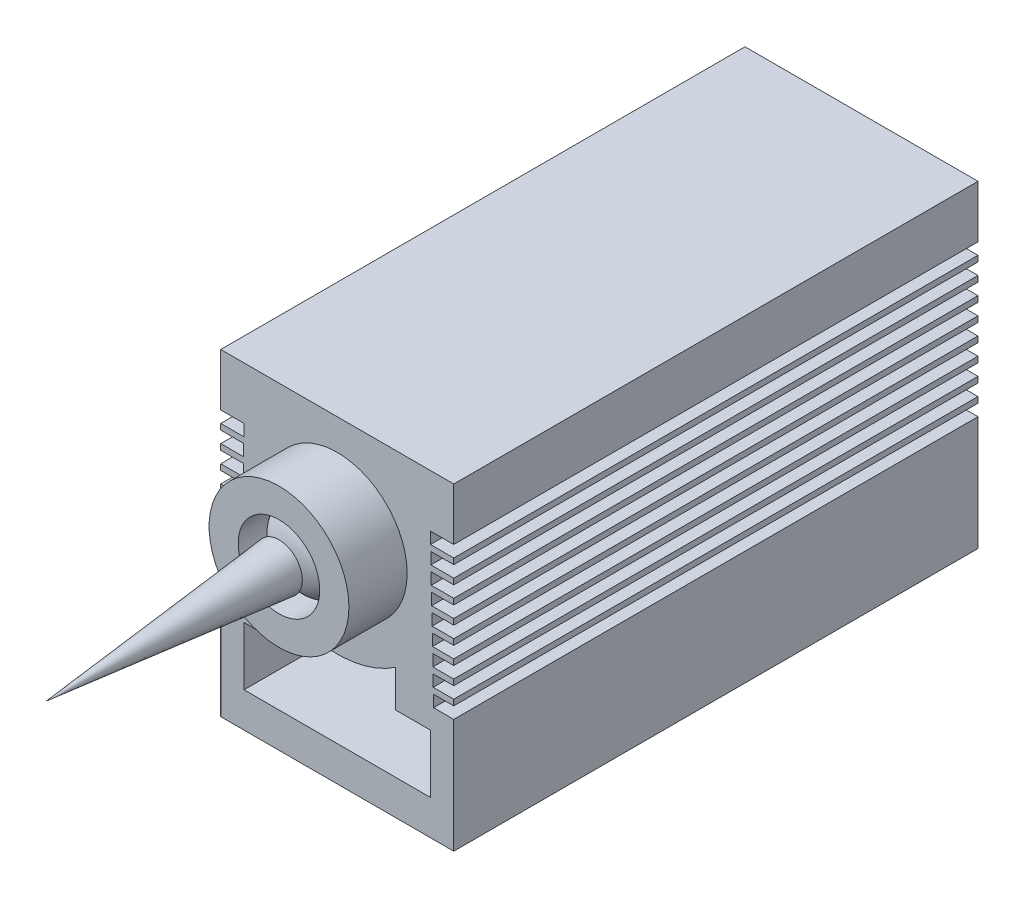
SolidWorks part; units mm, degrees
ref_plane "Alzado" through (0, 0, 0) normal (0, 0, 1) x (1, 0, 0)
ref_plane "Planta" through (0, 0, 0) normal (0, 1, 0) x (1, 0, 0)
ref_plane "Vista lateral" through (0, 0, 0) normal (1, 0, 0) x (0, 0, -1)
sketch "Croquis1" plane through (0, 0, 0) normal (0, 0, 1) x (1, 0, 0)
  line L1 (-10, 13.65) -> (10, 13.65)
  line L2 (-10, 13.65) -> (-10, -13.65)
  line L3 (-10, -13.65) -> (10, -13.65)
  line L4 (10, 13.65) -> (10, -13.65)
  line L5 (-10, 13.65) -> (10, -13.65) construction
  line L6 (-10, -13.65) -> (10, 13.65) construction
  point P0 (0, 0)
  dimension "D1" = 20
  dimension "D2" = 27.3
extrude "Saliente-Extruir1" add sketch "Croquis1" along normal blind 45
sketch "Croquis3" plane through (0, 0, 45) normal (0, 0, 1) x (1, 0, 0)
  circle A0 centre (0, 5) radius 6
  dimension "D1" = 12
  dimension "D2" = 5
extrude "Saliente-Extruir2" add sketch "Croquis3" along normal blind 5
sketch "Croquis4" plane through (0, 0, 45) normal (0, 0, 1) x (1, 0, 0)
  line L0 (-10, -13.65) -> (10, -13.65) construction
  line L1 (-8, -5.65) -> (8, -5.65)
  line L2 (-8, -5.65) -> (-8, -10.65)
  line L3 (-8, -10.65) -> (8, -10.65)
  line L4 (8, -5.65) -> (8, -10.65)
  line L5 (-8, -5.65) -> (8, -10.65) construction
  line L6 (-8, -10.65) -> (8, -5.65) construction
  line L7 (10, -13.65) -> (10, 13.65) construction
  line L8 (-10, 13.65) -> (-10, -13.65) construction
  line L9 (-5, -5.65) -> (-5, -2.4833)
  line L10 (0, 5) -> (0, -10.639) construction
  line L11 (5, -5.65) -> (5, -2.4833)
  circle A2 centre (0, 5) radius 9
  circle A3 centre (0, 5) radius 9
  point P0 (0, -8.15)
  dimension "D1" = 3
  dimension "D2" = 2
  dimension "D3" = 2
  dimension "D5" = 3
  dimension "D6" = 5
  dimension "D4" = 3
extrude "Cortar-Extruir1" cut sketch "Croquis4" against normal through all contours A3 L9 L1 L11 | L4 L1 L2 L3 region at (0, -8.15, 45) region at (0, -4.5349, 45)
sketch "Croquis5" plane through (0, 0, 50) normal (0, 0, 1) x (1, 0, 0)
  circle A0 centre (0, 5) radius 3.5
  dimension "D1" = 7
extrude "Cortar-Extruir2" cut sketch "Croquis5" against normal blind 3
dome "Cúpula1" faces to dome 1 distance 2 reverse direction no elliptical dome yes face at (3.5, 5, 47) parameters "D1"=2
sketch "Croquis6" plane through (0, 0, 45) normal (0, 0, 1) x (1, 0, 0)
  line L0 (0, 13.65) -> (0, -13.65) construction
  line L1 (10, 13.65) -> (-10, 13.65) construction
  line L2 (-10, -13.65) -> (10, -13.65) construction
  line L3 (-10, 13.65) -> (-10, -13.65) construction
  line L4 (-12, 9.15) -> (-8, 9.15)
  line L5 (-12, 9.15) -> (-12, 8.15)
  line L6 (-12, 8.15) -> (-8, 8.15)
  line L7 (-8, 9.15) -> (-8, 8.15)
  line L8 (-12, 9.15) -> (-8, 8.15) construction
  line L9 (-12, 8.15) -> (-8, 9.15) construction
  line L10 (-8.0338, 7.6504) -> (-8.0338, 6.6504)
  line L11 (-12.0338, 7.6504) -> (-8.0338, 7.6504)
  line L12 (-12.0338, 6.6504) -> (-8.0338, 6.6504)
  line L13 (-12.0338, 7.6504) -> (-12.0338, 6.6504)
  line L14 (-8.0676, 6.1508) -> (-8.0676, 5.1508)
  line L15 (-12.0676, 6.1508) -> (-8.0676, 6.1508)
  line L16 (-12.0676, 5.1508) -> (-8.0676, 5.1508)
  line L17 (-12.0676, 6.1508) -> (-12.0676, 5.1508)
  line L18 (-8.1014, 4.6511) -> (-8.1014, 3.6511)
  line L19 (-12.1014, 4.6511) -> (-8.1014, 4.6511)
  line L20 (-12.1014, 3.6511) -> (-8.1014, 3.6511)
  line L21 (-12.1014, 4.6511) -> (-12.1014, 3.6511)
  line L22 (-8.1352, 3.1515) -> (-8.1352, 2.1515)
  line L23 (-12.1352, 3.1515) -> (-8.1352, 3.1515)
  line L24 (-12.1352, 2.1515) -> (-8.1352, 2.1515)
  line L25 (-12.1352, 3.1515) -> (-12.1352, 2.1515)
  line L26 (-8.169, 1.6519) -> (-8.169, 0.6519)
  line L27 (-12.169, 1.6519) -> (-8.169, 1.6519)
  line L28 (-12.169, 0.6519) -> (-8.169, 0.6519)
  line L29 (-12.169, 1.6519) -> (-12.169, 0.6519)
  line L30 (-8.2029, 0.1523) -> (-8.2029, -0.8477)
  line L31 (-12.2029, 0.1523) -> (-8.2029, 0.1523)
  line L32 (-12.2029, -0.8477) -> (-8.2029, -0.8477)
  line L33 (-12.2029, 0.1523) -> (-12.2029, -0.8477)
  line L34 (-8.2367, -1.3473) -> (-8.2367, -2.3473)
  line L35 (-12.2367, -1.3473) -> (-8.2367, -1.3473)
  line L36 (-12.2367, -2.3473) -> (-8.2367, -2.3473)
  line L37 (-12.2367, -1.3473) -> (-12.2367, -2.3473)
  line L38 (-8.2705, -2.847) -> (-8.2705, -3.847)
  line L39 (-12.2705, -2.847) -> (-8.2705, -2.847)
  line L40 (-12.2705, -3.847) -> (-8.2705, -3.847)
  line L41 (-12.2705, -2.847) -> (-12.2705, -3.847)
  line L42 (8.2367, -1.3473) -> (8.2367, -2.3473)
  line L43 (8.2029, 0.1523) -> (8.2029, -0.8477)
  line L44 (12, 8.15) -> (8, 9.15) construction
  line L45 (12, 9.15) -> (8, 8.15) construction
  line L46 (8.169, 1.6519) -> (8.169, 0.6519)
  line L47 (8.1352, 3.1515) -> (8.1352, 2.1515)
  line L48 (8.1014, 4.6511) -> (8.1014, 3.6511)
  line L49 (8.0676, 6.1508) -> (8.0676, 5.1508)
  line L50 (12.0338, 7.6504) -> (12.0338, 6.6504)
  line L51 (12.0338, 6.6504) -> (8.0338, 6.6504)
  line L52 (12.0338, 7.6504) -> (8.0338, 7.6504)
  line L53 (8.0338, 7.6504) -> (8.0338, 6.6504)
  line L54 (8, 9.15) -> (8, 8.15)
  line L55 (12, 8.15) -> (8, 8.15)
  line L56 (12, 9.15) -> (12, 8.15)
  line L57 (12, 9.15) -> (8, 9.15)
  line L58 (12.2705, -2.847) -> (12.2705, -3.847)
  line L59 (12.2705, -3.847) -> (8.2705, -3.847)
  line L60 (12.2705, -2.847) -> (8.2705, -2.847)
  line L61 (8.2705, -2.847) -> (8.2705, -3.847)
  line L62 (12.2367, -1.3473) -> (12.2367, -2.3473)
  line L63 (12.2367, -2.3473) -> (8.2367, -2.3473)
  line L64 (12.2367, -1.3473) -> (8.2367, -1.3473)
  line L65 (12.2029, 0.1523) -> (12.2029, -0.8477)
  line L66 (12.2029, -0.8477) -> (8.2029, -0.8477)
  line L67 (12.2029, 0.1523) -> (8.2029, 0.1523)
  line L68 (12.169, 1.6519) -> (12.169, 0.6519)
  line L69 (12.169, 0.6519) -> (8.169, 0.6519)
  line L70 (12.169, 1.6519) -> (8.169, 1.6519)
  line L71 (12.1352, 3.1515) -> (12.1352, 2.1515)
  line L72 (12.1352, 2.1515) -> (8.1352, 2.1515)
  line L73 (12.1352, 3.1515) -> (8.1352, 3.1515)
  line L74 (12.1014, 4.6511) -> (12.1014, 3.6511)
  line L75 (12.1014, 3.6511) -> (8.1014, 3.6511)
  line L76 (12.1014, 4.6511) -> (8.1014, 4.6511)
  line L77 (12.0676, 6.1508) -> (12.0676, 5.1508)
  line L78 (12.0676, 5.1508) -> (8.0676, 5.1508)
  line L79 (12.0676, 6.1508) -> (8.0676, 6.1508)
  point P6 (-10, 8.65)
  point P65 (10, 8.65)
  dimension "D1" = 5
  dimension "D2" = 1
  dimension "D3" = 4
  dimension "D4" = 9
extrude "Cortar-Extruir3" cut sketch "Croquis6" against normal through all
sketch "Croquis7" plane through (0, 0, 0) normal (0, 0, -1) x (-1, 0, 0)
  line L0 (-10, 13.65) -> (10, 13.65) construction
  circle A0 centre (0, 3.3) radius 6.35
  point P3 (0, 9.65)
  dimension "D1" = 12.7
  dimension "D2" = 4
extrude "Cortar-Extruir4" cut sketch "Croquis7" against normal blind 3
ref_axis "Eje1" through (0, 5, 50) along (0, 0, -1)
sketch "Croquis8" plane through (0, 0, 0) normal (1, 0, 0) x (0, 0, -1)
  line L0 (-50, 5) -> (-70, 5) construction
  line L1 (-50, 11) -> (-50, -1) construction
  line L2 (-50, 5) -> (-45, 5) construction
  line L3 (-70, 5) -> (-50, 7)
  line L5 (-50, 7) -> (-50, 5)
  line L6 (-50, 5) -> (-70, 5)
  dimension "D1" = 20
  dimension "D2" = 5.711
revolve "Revolución1" add sketch "Croquis8" angle 360 about L0
